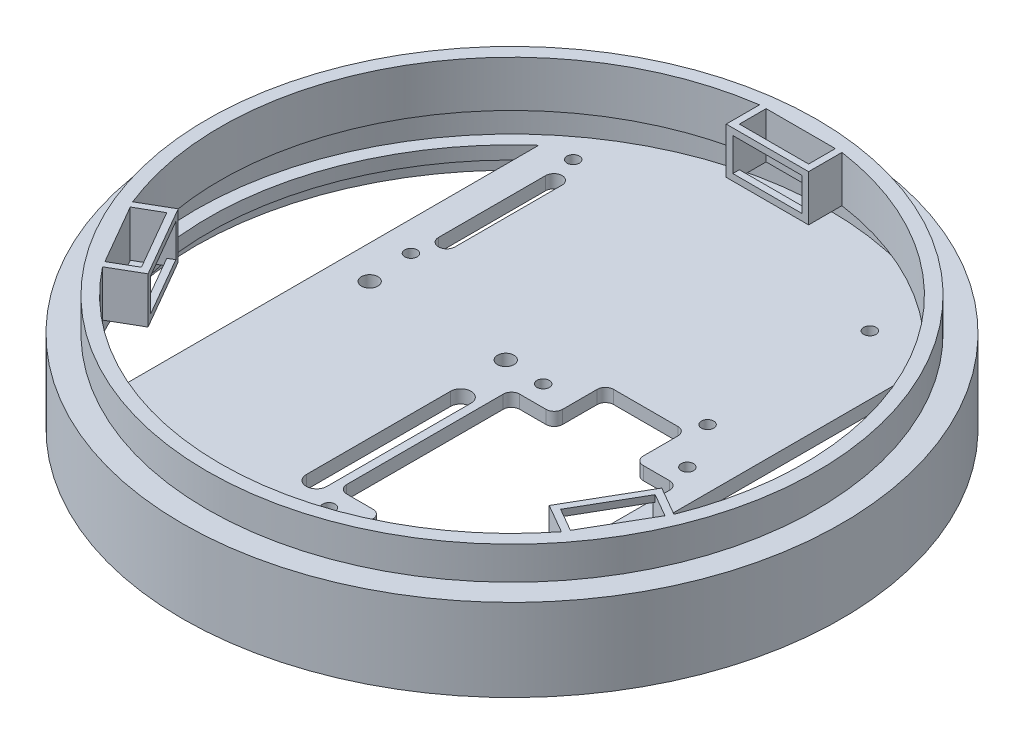
SolidWorks part; units mm, degrees
ref_plane "Front Plane" through (0, 0, 0) normal (0, 0, 1) x (1, 0, 0)
ref_plane "Top Plane" through (0, 0, 0) normal (0, 1, 0) x (1, 0, 0)
ref_plane "Right Plane" through (0, 0, 0) normal (1, 0, 0) x (0, 0, -1)
sketch "Sketch1" plane through (0, 0, 0) normal (0, 1, 0) x (1, 0, 0)
  circle A0 centre (0, 0) radius 40
  dimension "D1" = 80
extrude "Boss-Extrude1" add sketch "Sketch1" along normal blind 10
sketch "Sketch2" plane through (0, 10, 0) normal (0, 1, 0) x (1, 0, 0)
  circle A2 centre (0, 0) radius 37
  circle A3 centre (0, 0) radius 37
  dimension "D1" = 3
extrude "Boss-Extrude2" add sketch "Sketch2" along normal blind 4
shell "Shell1" thickness 1.6 removed face at (0, 0, 40)
ref_plane "Plane1" through (0, 3.8, 0) normal (0, -1, 0) x (-1, 0, 0)
sketch "Sketch4" plane through (0, 14, 0) normal (0, 1, 0) x (1, 0, 0)
  circle A2 centre (0, 0) radius 35.4
  circle A3 centre (0, 0) radius 35.4
  dimension "D1" = 1.6
extrude "Cut-Extrude2" cut sketch "Sketch4" against normal up to surface (5.6 mm away) up to face at (0, 8.4, 35.4)
sketch "Sketch5" plane through (0, 3.8, 0) normal (0, -1, 0) x (-1, 0, 0)
  circle A0 centre (0, 0) radius 38.4 construction
  circle A1 centre (0, 0) radius 38.4
extrude "Boss-Extrude3" add sketch "Sketch5" along normal blind 1.6
sketch "Sketch3" plane through (0, 3.8, 0) normal (0, 1, 0) x (1, 0, 0)
  line L0 (-22.7473, 5.4807) -> (-1.3473, 5.4807) construction
  line L1 (-22.7473, 5.4807) -> (-22.7473, -30.2193) construction
  line L2 (-1.3473, 5.4807) -> (-1.3473, -30.2193) construction
  line L3 (-22.7473, -30.2193) -> (-1.3473, -30.2193) construction
  line L4 (-22.7473, 5.4807) -> (-1.3473, -30.2193) construction
  line L5 (-1.3473, 5.4807) -> (-22.7473, -30.2193) construction
  line L6 (20.8527, -31.7193) -> (-1.3473, -31.7193) construction
  line L7 (20.8527, -31.7193) -> (20.8527, 6.4807) construction
  line L8 (-1.3473, -31.7193) -> (-1.3473, 6.4807) construction
  line L9 (20.8527, 6.4807) -> (-1.3473, 6.4807) construction
  line L10 (20.8527, -31.7193) -> (-1.3473, 6.4807) construction
  line L11 (-1.3473, -31.7193) -> (20.8527, 6.4807) construction
  line L12 (17.2527, 6.4807) -> (-22.7473, 6.4807) construction
  line L13 (17.2527, 6.4807) -> (17.2527, 30.1807) construction
  line L14 (-22.7473, 6.4807) -> (-22.7473, 30.1807) construction
  line L15 (17.2527, 30.1807) -> (-22.7473, 30.1807) construction
  line L16 (17.2527, 6.4807) -> (-22.7473, 30.1807) construction
  line L17 (-22.7473, 6.4807) -> (17.2527, 30.1807) construction
  line L18 (-40, 0) -> (40, 0) construction
  circle A0 centre (0, 0) radius 40 construction
  text T0 "P"
  text T1 "R"
  point P1 (-12.0473, -12.3693)
  point P2 (9.7527, -12.6193)
  point P3 (-2.7473, 18.3307)
  point P20 (-33.8862, -45.2136)
  point P21 (6.7411, -15.1986)
  point P22 (0, 19.9136)
  point P23 (12.5684, -11.267)
  point P24 (-9.139, -11.267)
  point P25 (0, 0)
  point P26 (8.6682, -10.359)
  point P27 (-14.5275, -9.5706)
  point P28 (-55.3911, -29.2046)
  point P29 (-49.8157, -14.4636)
  point P30 (9.6502, -12.9453)
  point P31 (8.9906, -12.0259)
  point P32 (-15.0372, -11.3164)
  point P33 (-3.048, 18.1785)
  dimension "D1" = 21.4
  dimension "D2" = 35.7
  dimension "D3" = 22.2
  dimension "D4" = 38.2
  dimension "D5" = 23.7
  dimension "D6" = 40
  dimension "D7" = 1
  dimension "D8" = 6.4807
  dimension "D9" = 22.7473
sketch "Sketch6" plane through (0, 3.8, 0) normal (0, 1, 0) x (1, 0, 0)
  line L0 (-22.7473, 5.4807) -> (-1.3473, 5.4807) construction
  line L1 (-1.3473, 5.4807) -> (-1.3473, -30.2193) construction
  line L2 (-22.7473, -30.2193) -> (-1.3473, -30.2193) construction
  line L3 (-22.7473, 5.4807) -> (-22.7473, -30.2193) construction
  line L4 (-22.7473, 5.4807) -> (-1.3473, 5.4807) construction
  line L5 (-1.3473, 5.4807) -> (-1.3473, -30.2193) construction
  line L6 (-22.7473, -30.2193) -> (-1.3473, -30.2193) construction
  line L7 (-22.7473, 5.4807) -> (-22.7473, -30.2193) construction
  line L8 (-12.0473, -30.2193) -> (-12.0473, 5.4807) construction
  line L9 (-3.7923, 3.0307) -> (-20.3023, 3.0307) construction
  line L10 (-5.4623, -27.7693) -> (-18.6323, -27.7693) construction
  line L11 (-1.3473, -2.3693) -> (-1.3473, -22.3693)
  line L12 (-1.3473, -2.3693) -> (-3.8473, -2.3693)
  line L13 (-1.3473, -22.3693) -> (-3.8473, -22.3693)
  line L14 (-3.8473, -2.3693) -> (-3.8473, -22.3693)
  circle A0 centre (-3.7923, 3.0307) radius 1
  circle A1 centre (-20.3023, 3.0307) radius 1
  circle A2 centre (-5.4623, -27.7693) radius 1
  circle A3 centre (-18.6323, -27.7693) radius 1
  point P10 (-12.0473, 3.0307)
  point P15 (-1.3473, -10.0197)
  point P16 (-1.3473, -12.3693)
  point P17 (-12.0473, -27.7693)
  point P18 (-1.3473, -12.3693)
  dimension "D1" = 2
  dimension "D4" = 13.17
  dimension "D5" = 2.45
  dimension "D2" = 2.45
  dimension "D3" = 16.51
  dimension "D6" = 2.5
  dimension "D7" = 20
extrude "Cut-Extrude3" cut sketch "Sketch6" against normal up to surface (1.6 mm away) up to face at (0, 2.2, -38.4)
fillet "Fillet1" 2 edges at (-1.3473, 3, 2.3693) (-3.8473, 3, 2.3693) type full round first side face at (-1.3473, 3, 12.3693) second side face at (-3.8473, 3, 12.3693) middle face at (-2.5973, 3, 2.3693)
fillet "Fillet2" 2 edges at (-1.3473, 3, 22.3693) (-3.8473, 3, 22.3693) type full round first side face at (-1.3473, 3, 12.9943) second side face at (-3.8473, 3, 12.9943) middle face at (-2.5973, 3, 22.3693)
sketch "Sketch8" plane through (0, 3.8, 0) normal (0, 1, 0) x (1, 0, 0)
  line L0 (20.8527, -31.7193) -> (-1.3473, -31.7193) construction
  line L1 (20.8527, -31.7193) -> (20.8527, 6.4807) construction
  line L2 (20.8527, 6.4807) -> (-1.3473, 6.4807) construction
  line L3 (-1.3473, -31.7193) -> (-1.3473, 6.4807) construction
  line L4 (20.8527, -31.7193) -> (-1.3473, -31.7193) construction
  line L5 (20.8527, -31.7193) -> (20.8527, 6.4807) construction
  line L6 (20.8527, 6.4807) -> (-1.3473, 6.4807) construction
  line L7 (-1.3473, -31.7193) -> (-1.3473, 6.4807) construction
  line L8 (9.7527, -31.7193) -> (9.7527, 6.4807) construction
  line L9 (18.5027, -23.2193) -> (1.0027, -23.2193) construction
  line L10 (1.0027, -23.2193) -> (1.0027, 2.7807) construction
  line L11 (1.0027, 2.7807) -> (18.5027, 2.7807) construction
  line L12 (18.5027, 2.7807) -> (18.5027, -23.2193) construction
  line L13 (4.8525, -31.7193) -> (4.8525, -20.7193)
  line L14 (4.8525, -31.7193) -> (14.6528, -31.7193)
  line L15 (4.8525, 6.4807) -> (14.6528, 6.4807)
  line L16 (14.6528, -31.7193) -> (14.6528, -20.7193)
  line L17 (4.8525, -31.7193) -> (14.6528, 6.4807) construction
  line L18 (4.8525, 6.4807) -> (14.6528, -31.7193) construction
  line L19 (-0.3473, -20.7193) -> (4.8525, -20.7193)
  line L20 (-0.3473, -20.7193) -> (-0.3473, 0.2807)
  line L21 (19.8527, -20.7193) -> (19.8527, 0.2807)
  line L22 (-0.3473, 0.2807) -> (4.8525, 0.2807)
  line L23 (-0.3473, -20.7193) -> (19.8527, 0.2807) construction
  line L24 (19.8527, -20.7193) -> (-0.3473, 0.2807) construction
  line L25 (14.6528, 0.2807) -> (14.6528, 6.4807)
  line L26 (4.8525, 0.2807) -> (4.8525, 6.4807)
  line L27 (14.6528, 0.2807) -> (19.8527, 0.2807)
  line L28 (14.6528, -20.7193) -> (19.8527, -20.7193)
  circle A0 centre (18.5027, -23.2193) radius 0.75
  circle A1 centre (1.0027, -23.2193) radius 0.75
  circle A2 centre (1.0027, 2.7807) radius 0.75
  circle A3 centre (18.5027, 2.7807) radius 0.75
  point P11 (9.7527, -23.2193)
  point P15 (0, 0)
  point P16 (9.7527, -12.6193)
  point P17 (9.7527, -10.2193)
  point P22 (0, 0)
  point P23 (18.5027, -10.2193)
  point P28 (0, 0)
  point P29 (1.2686, -10.5219)
  dimension "D1" = 1.5
  dimension "D2" = 17.5
  dimension "D3" = 26
  dimension "D4" = 8.5
  dimension "D5" = 9.8003
  dimension "D6" = 1
  dimension "D7" = 21
extrude "Cut-Extrude4" cut sketch "Sketch8" against normal up to surface (1.6 mm away) up to face at (-2.5973, 2.2, 12.3693)
fillet "Fillet3" radius 1 12 edges at (14.6528, 3, 20.7193) (4.8525, 3, 20.7193) (4.8525, 3, -0.2807) (14.6528, 3, -0.2807) (4.8525, 3, -6.4807) (14.6528, 3, -6.4807) (19.8527, 3, -0.2807) (-0.3473, 3, -0.2807) (-0.3473, 3, 20.7193) (4.8525, 3, 31.7193) (14.6528, 3, 31.7193) (19.8527, 3, 20.7193)
sketch "Sketch9" plane through (0, 3.8, 0) normal (0, 1, 0) x (1, 0, 0)
  line L0 (-22.7473, 6.4807) -> (-22.7473, 30.1807) construction
  line L1 (17.2527, 30.1807) -> (-22.7473, 30.1807) construction
  line L2 (17.2527, 6.4807) -> (17.2527, 30.1807) construction
  line L3 (17.2527, 6.4807) -> (-22.7473, 6.4807) construction
  line L4 (-22.7473, 6.4807) -> (-22.7473, 30.1807) construction
  line L5 (17.2527, 30.1807) -> (-22.7473, 30.1807) construction
  line L6 (17.2527, 6.4807) -> (17.2527, 30.1807) construction
  line L7 (17.2527, 6.4807) -> (-22.7473, 6.4807) construction
  line L8 (17.2527, 18.3307) -> (-22.7473, 18.3307) construction
  line L9 (-2.7473, 30.1807) -> (-2.7473, 6.4807) construction
  line L10 (-18.7473, 25.8307) -> (-18.7473, 10.8307)
  line L11 (-18.7473, 25.8307) -> (-20.7473, 25.8307)
  line L12 (-18.7473, 10.8307) -> (-20.7473, 10.8307)
  line L13 (-20.7473, 25.8307) -> (-20.7473, 10.8307)
  line L14 (-18.7473, 25.8307) -> (-20.7473, 10.8307) construction
  line L15 (-18.7473, 10.8307) -> (-20.7473, 25.8307) construction
  circle A0 centre (15.2527, 28.1807) radius 0.75
  circle A1 centre (-20.7473, 28.1807) radius 0.75
  circle A2 centre (15.2527, 8.4807) radius 0.75
  circle A3 centre (-20.7473, 8.4807) radius 0.75
  point P10 (16.0027, 28.1807)
  point P11 (15.2527, 28.9307)
  point P18 (0, 0)
  point P19 (-19.7473, 18.3307)
  dimension "D3" = 1.5
  dimension "D1" = 1.25
  dimension "D2" = 1.25
  dimension "D4" = 2
  dimension "D5" = 1
  dimension "D6" = 15
extrude "Cut-Extrude5" cut sketch "Sketch9" against normal up to surface (1.6 mm away) up to face at (1.0027, 2.2, -3.5307)
fillet "Fillet4" 2 edges at (-18.7473, 3, -10.8307) (-20.7473, 3, -10.8307) type full round first side face at (-18.7473, 3, -18.3307) second side face at (-20.7473, 3, -18.3307) middle face at (-19.7473, 3, -10.8307)
fillet "Fillet5" 2 edges at (-20.7473, 3, -25.8307) (-18.7473, 3, -25.8307) type full round first side face at (-20.7473, 3, -18.8307) second side face at (-18.7473, 3, -18.8307) middle face at (-19.7473, 3, -25.8307)
sketch "Sketch11" plane through (0, 3.8, 0) normal (0, 1, 0) x (1, 0, 0)
  line L0 (22.4527, 29.1568) -> (22.4527, -29.1568)
  line L1 (-24.3473, -27.5943) -> (-24.3473, 27.5943)
  line L2 (22.4527, -31.7193) -> (22.4527, 6.4807)
  line L3 (22.4527, -31.7193) -> (22.4527, 6.4807) construction
  line L5 (-24.3473, 5.4807) -> (-24.3473, -30.2193)
  line L6 (-24.3473, 5.4807) -> (-24.3473, -30.2193) construction
  arc A0 (22.4527, -29.1568) -> (22.4527, 29.1568) centre (0, 0) ccw
  circle A2 centre (0, 0) radius 36.8
  arc A3 (-24.3473, 27.5943) -> (-24.3473, -27.5943) centre (0, 0) ccw
  point P14 (30.7038, 20.2858)
  point P15 (-8.0046, 35.9189)
  dimension "D1" = 1.6
  dimension "D2" = 1.6
  dimension "D3" = 1.6
extrude "Cut-Extrude6" cut sketch "Sketch11" against normal up to surface (1.6 mm away) up to face at (-19.7473, 2.2, -18.3307)
ref_plane "Plane2" through (0, 0, -31) normal (0, 0, 1) x (1, 0, 0)
sketch "Sketch12" plane through (0, 0, -31) normal (0, 0, 1) x (1, 0, 0)
  line L0 (0, 14) -> (0, 8.4) construction
  line L1 (-14.7159, 8.4) -> (16.2195, 8.4) construction
  line L2 (-35.4, 8.4) -> (35.4, 8.4) construction
  line L3 (35.4, 14) -> (-35.4, 14) construction
  line L4 (-5, 14) -> (-5, 8.4)
  line L5 (-5, 14) -> (5, 14)
  line L6 (-5, 8.4) -> (5, 8.4)
  line L7 (5, 14) -> (5, 8.4)
  line L8 (-5, 14) -> (5, 8.4) construction
  line L9 (-5, 8.4) -> (5, 14) construction
  point P7 (0, 0)
  point P8 (0, 0)
  point P12 (0, 11.2)
  dimension "D1" = 10
extrude "Boss-Extrude4" add sketch "Sketch12" against normal up to body separate body
sketch "Sketch13" plane through (0, 14, 0) normal (0, 1, 0) x (1, 0, 0)
  line L0 (-5, 35.0451) -> (5, 35.0451) construction
  line L5 (-4.2, 35.0451) -> (4.2, 35.0451)
  line L8 (4.2, 31.8) -> (4.2, 35.0451)
  line L9 (-4.2, 31.8) -> (4.2, 31.8)
  line L10 (-4.2, 35.0451) -> (-4.2, 31.8)
  line L11 (4.2, 31.8) -> (4.2, 35.0451)
  line L12 (-4.2, 31.8) -> (4.2, 31.8)
  line L13 (-4.2, 35.0451) -> (-4.2, 31.8)
  dimension "D1" = 0.8
extrude "Cut-Extrude7" cut sketch "Sketch13" against normal up to surface (5.6 mm away) up to face at (0, 8.4, -15.4113)
sketch "Sketch14" plane through (0, 0, -31) normal (0, 0, 1) x (1, 0, 0)
  line L8 (4.2, 13.2) -> (-4.2, 13.2)
  line L9 (-4.2, 13.2) -> (-4.2, 9.2)
  line L10 (-4.2, 9.2) -> (4.2, 9.2)
  line L11 (4.2, 9.2) -> (4.2, 13.2)
  line L12 (4.2, 13.2) -> (-4.2, 13.2)
  line L13 (-4.2, 13.2) -> (-4.2, 9.2)
  line L14 (-4.2, 9.2) -> (4.2, 9.2)
  line L15 (4.2, 9.2) -> (4.2, 13.2)
  dimension "D1" = 0.8
extrude "Cut-Extrude8" cut sketch "Sketch14" against normal up to surface (0.8 mm away) up to face at (0, 11.2, -31.8)
pattern_circular "CirPattern3" count 3 over 360 about axis through (0, 10, 0) along (0, -1, 0) of "Boss-Extrude4", "Cut-Extrude7", "Cut-Extrude8"
